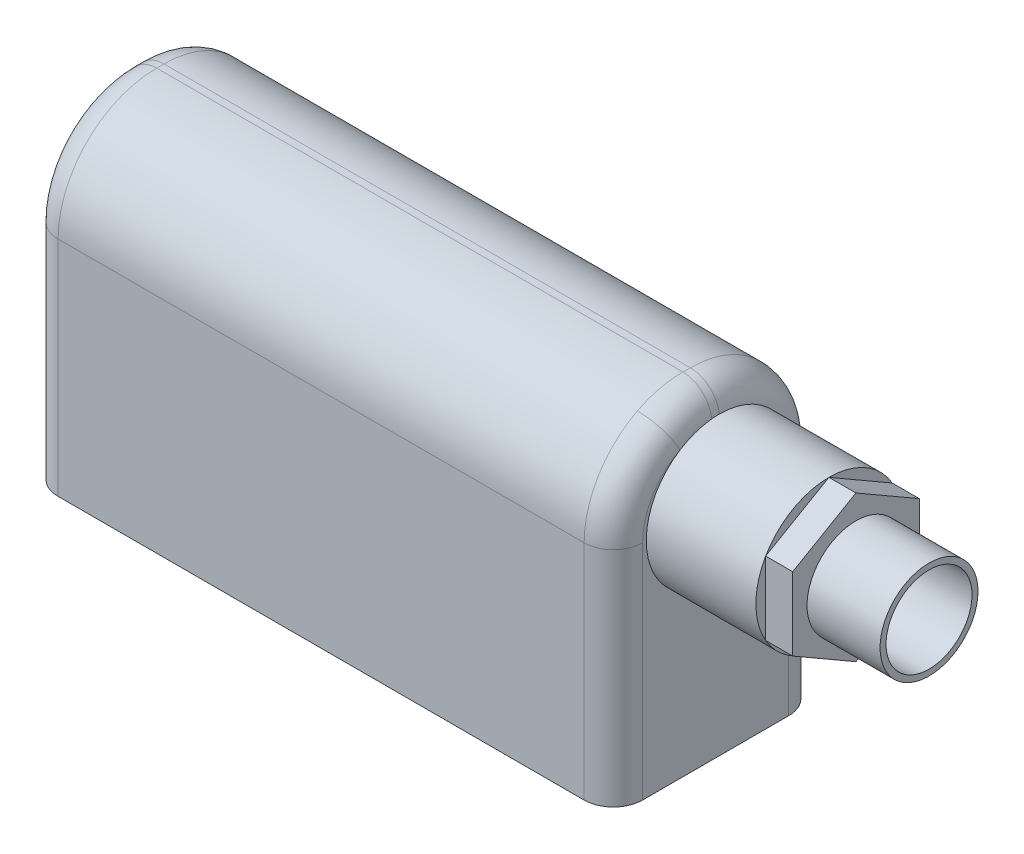
SolidWorks part; units mm, degrees
ref_plane "前视基准面" through (0, 0, 0) normal (0, 0, 1) x (1, 0, 0)
ref_plane "上视基准面" through (0, 0, 0) normal (0, 1, 0) x (1, 0, 0)
ref_plane "右视基准面" through (0, 0, 0) normal (1, 0, 0) x (0, 0, -1)
sketch "草图1" plane through (0, 0, 0) normal (0, 0, 1) x (1, 0, 0)
  line L1 (-40, -22) -> (40, -22)
  line L2 (-40, -22) -> (-40, 22)
  line L3 (-40, 22) -> (40, 22)
  line L4 (40, -22) -> (40, 22)
  line L5 (-40, -22) -> (40, 22) construction
  line L6 (-40, 22) -> (40, -22) construction
  point P0 (0, 0)
  dimension "D1" = 80
  dimension "D2" = 44
extrude "凸台-拉伸1" add sketch "草图1" along normal blind 28 contours L3 L4 L1 L2
fillet "圆角1" radius 13.5 1 edges at (0, 22, 28)
fillet "圆角2" radius 13.5 1 edges at (0, 22, 0)
sketch "草图2" plane through (40, 0, 0) normal (1, 0, 0) x (0, 0, -1)
  circle A0 centre (-13.5, 8.5) radius 10
extrude "凸台-拉伸2" add sketch "草图2" along normal blind 15
sketch "草图3" plane through (55, 0, 0) normal (1, 0, 0) x (0, 0, -1)
  line L1 (-13.5, 18.5) -> (-22.1603, 13.5)
  line L2 (-22.1603, 13.5) -> (-22.1603, 3.5)
  line L3 (-22.1603, 3.5) -> (-13.5, -1.5)
  line L4 (-13.5, -1.5) -> (-4.8397, 3.5)
  line L5 (-4.8397, 3.5) -> (-4.8397, 13.5)
  line L6 (-4.8397, 13.5) -> (-13.5, 18.5)
  circle A0 centre (-13.5, 8.5) radius 8.6603 construction
extrude "凸台-拉伸3" add sketch "草图3" along normal blind 3.7
sketch "草图4" plane through (58.7, 0, 0) normal (1, 0, 0) x (0, 0, -1)
  circle A0 centre (-13.5, 8.5) radius 6.7
extrude "凸台-拉伸4" add sketch "草图4" along normal blind 10
sketch "草图5" plane through (68.7, 0, 0) normal (1, 0, 0) x (0, 0, -1)
  circle A0 centre (-13.5, 8.5) radius 5.8831
extrude "切除-拉伸1" cut sketch "草图5" against normal blind 20
fillet "圆角3" radius 4 8 edges at (40, -6.75, 0) (40, 18.0459, 24.0459) (-40, -6.75, 0) (-40, 18.0459, 3.9541) (-40, 22, 14) (-40, 18.0459, 24.0459) (40, -6.75, 28) (-40, -6.75, 28)
sketch "草图7" plane through (0, -22, 0) normal (0, -1, 0) x (1, 0, 0)
  line L8 (-36, 2) -> (36, 2)
  line L9 (38, 4) -> (38, 24)
  line L10 (36, 26) -> (-36, 26)
  line L11 (-38, 24) -> (-38, 4)
  line L12 (-36, 2) -> (36, 2)
  line L13 (38, 4) -> (38, 24)
  line L14 (36, 26) -> (-36, 26)
  line L15 (-38, 24) -> (-38, 4)
  arc A8 (36, 2) -> (38, 4) centre (36, 4) ccw
  arc A9 (38, 24) -> (36, 26) centre (36, 24) ccw
  arc A10 (-36, 26) -> (-38, 24) centre (-36, 24) ccw
  arc A11 (-38, 4) -> (-36, 2) centre (-36, 4) ccw
  arc A12 (36, 2) -> (38, 4) centre (36, 4) ccw
  arc A13 (38, 24) -> (36, 26) centre (36, 24) ccw
  arc A14 (-36, 26) -> (-38, 24) centre (-36, 24) ccw
  arc A15 (-38, 4) -> (-36, 2) centre (-36, 4) ccw
  dimension "D1" = 2
extrude "切除-拉伸2" cut sketch "草图7" against normal blind 8.5
sketch "草图8" plane through (0, -13.5, 0) normal (0, -1, 0) x (1, 0, 0)
  line L0 (-38, 14) -> (38, 14) construction
  line L1 (-38, 24) -> (-38, 4) construction
  line L2 (38, 4) -> (38, 24) construction
  line L3 (0, 26) -> (0, 2) construction
  line L4 (36, 26) -> (-36, 26) construction
  line L5 (-36, 2) -> (36, 2) construction
  line L6 (-18, 16) -> (-18, 20)
  line L7 (-18, 8) -> (18, 8)
  line L8 (-18, 8) -> (-18, 12)
  line L9 (-18, 20) -> (18, 20)
  line L10 (18, 8) -> (18, 12)
  line L11 (-18, 8) -> (18, 20) construction
  line L12 (-18, 20) -> (18, 8) construction
  line L13 (18, 16) -> (22.5, 16)
  line L14 (-18, 16) -> (-22.5, 16)
  line L15 (18, 16) -> (18, 20)
  line L16 (-18, 12) -> (-22.5, 12)
  line L17 (-22.5, 16) -> (-22.5, 12)
  line L19 (18, 12) -> (22.5, 12)
  line L20 (22.5, 16) -> (22.5, 12)
  point P12 (0, 14)
  dimension "D1" = 36
  dimension "D2" = 12
  dimension "D3" = 4.5
  dimension "D4" = 4.5
  dimension "D5" = 2
  dimension "D6" = 4
  dimension "D7" = 2
  dimension "D8" = 4
extrude "凸台-拉伸5" add sketch "草图8" along normal blind 14
fillet "圆角4" radius 3 1 edges at (0, -27.5, 20)
fillet "圆角5" radius 3 1 edges at (0, -27.5, 8)
sketch "草图9" plane through (0, -13.5, 0) normal (0, -1, 0) x (1, 0, 0)
  line L0 (-38, 14) -> (38, 14) construction
  line L1 (-38, 24) -> (-38, 4) construction
  line L2 (38, 4) -> (38, 24) construction
  line L3 (0, 26) -> (0, 0.7936) construction
  line L4 (36, 26) -> (-36, 26) construction
  circle A0 centre (-24.3, 20) radius 1.5
  circle A1 centre (-18.9, 20) radius 1.5
  circle A2 centre (-13.5, 20) radius 1.5
  circle A3 centre (-8.1, 20) radius 1.5
  circle A4 centre (-2.7, 20) radius 1.5
  circle A5 centre (2.7, 20) radius 1.5
  circle A6 centre (8.1, 20) radius 1.5
  circle A7 centre (13.5, 20) radius 1.5
  circle A8 centre (18.9, 20) radius 1.5
  circle A9 centre (24.3, 20) radius 1.5
  circle A10 centre (-24.3, 8) radius 1.5
  circle A11 centre (-18.9, 8) radius 1.5
  circle A12 centre (-13.5, 8) radius 1.5
  circle A13 centre (-8.1, 8) radius 1.5
  circle A14 centre (-2.7, 8) radius 1.5
  circle A15 centre (2.7, 8) radius 1.5
  circle A16 centre (8.1, 8) radius 1.5
  circle A17 centre (13.5, 8) radius 1.5
  circle A18 centre (18.9, 8) radius 1.5
  circle A19 centre (24.3, 8) radius 1.5
  dimension "D1" = 24.3
  dimension "D2" = 6
  dimension "D3" = 10
  dimension "D4" = 2
extrude "切除-拉伸3" cut sketch "草图9" against normal blind 4
ref_axis "基准轴1" through (48.7, 8.5, 13.5) along (1, 0, 0)
sketch "0_0_Point" plane through (0, -9.5, 0) normal (0, -1, 0) x (1, 0, 0)
  point P0 (24.2869, 8.1168)
sketch "1_0_Point" plane through (0, -9.5, 0) normal (0, -1, 0) x (1, 0, 0)
  point P0 (19.0783, 7.9371)
sketch "2_0_Point" plane through (0, -9.5, 0) normal (0, -1, 0) x (1, 0, 0)
  point P0 (13.2411, 7.6677)
sketch "3_0_Point" plane through (0, -9.5, 0) normal (0, -1, 0) x (1, 0, 0)
  point P0 (7.9427, 7.4881)
sketch "4_0_Point" plane through (0, -9.5, 0) normal (0, -1, 0) x (1, 0, 0)
  point P0 (2.5545, 7.4881)
sketch "5_0_Point" plane through (0, -9.5, 0) normal (0, -1, 0) x (1, 0, 0)
  point P0 (-2.9236, 7.6677)
sketch "6_0_Point" plane through (0, -9.5, 0) normal (0, -1, 0) x (1, 0, 0)
  point P0 (-8.3118, 7.5779)
sketch "7_0_Point" plane through (0, -9.5, 0) normal (0, -1, 0) x (1, 0, 0)
  point P0 (-13.6102, 7.4881)
sketch "8_0_Point" plane through (0, -9.5, 0) normal (0, -1, 0) x (1, 0, 0)
  point P0 (-18.8188, 8.1168)
sketch "9_0_Point" plane through (0, -9.5, 0) normal (0, -1, 0) x (1, 0, 0)
  point P0 (-24.2968, 8.2066)
sketch "10_0_Point" plane through (0, -9.5, 0) normal (0, -1, 0) x (1, 0, 0)
  point P0 (24.1073, 20.0606)
sketch "11_0_Point" plane through (0, -9.5, 0) normal (0, -1, 0) x (1, 0, 0)
  point P0 (18.8987, 20.0606)
sketch "12_0_Point" plane through (0, -9.5, 0) normal (0, -1, 0) x (1, 0, 0)
  point P0 (13.4207, 20.5096)
sketch "13_0_Point" plane through (0, -9.5, 0) normal (0, -1, 0) x (1, 0, 0)
  point P0 (7.9427, 20.5096)
sketch "14_0_Point" plane through (0, -9.5, 0) normal (0, -1, 0) x (1, 0, 0)
  point P0 (2.5545, 20.7791)
sketch "15_0_Point" plane through (0, -9.5, 0) normal (0, -1, 0) x (1, 0, 0)
  point P0 (-2.744, 20.7791)
sketch "16_0_Point" plane through (0, -9.5, 0) normal (0, -1, 0) x (1, 0, 0)
  point P0 (-8.4016, 20.7791)
sketch "17_0_Point" plane through (0, -9.5, 0) normal (0, -1, 0) x (1, 0, 0)
  point P0 (-13.6102, 20.5994)
sketch "18_0_Point" plane through (0, -9.5, 0) normal (0, -1, 0) x (1, 0, 0)
  point P0 (-19.0882, 19.9708)
sketch "19_0_Point" plane through (0, -9.5, 0) normal (0, -1, 0) x (1, 0, 0)
  point P0 (-24.3866, 20.1504)
other "0_0"
ref_axis "基准轴2" through (24.2869, 0.5, 8.1168) along (0, -1, 0)
other "1_0"
ref_axis "基准轴3" through (19.0783, 0.5, 7.9371) along (0, -1, 0)
other "2_0"
ref_axis "基准轴4" through (13.2411, 0.5, 7.6677) along (0, -1, 0)
other "3_0"
ref_axis "基准轴5" through (7.9427, 0.5, 7.4881) along (0, -1, 0)
other "4_0"
ref_axis "基准轴6" through (2.5545, 0.5, 7.4881) along (0, -1, 0)
other "5_0"
ref_axis "基准轴7" through (-2.9236, 0.5, 7.6677) along (0, -1, 0)
other "6_0"
ref_axis "基准轴8" through (-8.3118, 0.5, 7.5779) along (0, -1, 0)
other "7_0"
ref_axis "基准轴9" through (-13.6102, 0.5, 7.4881) along (0, -1, 0)
other "8_0"
ref_axis "基准轴10" through (-18.8188, 0.5, 8.1168) along (0, -1, 0)
other "9_0"
ref_axis "基准轴11" through (-24.2968, 0.5, 8.2066) along (0, -1, 0)
other "10_0"
ref_axis "基准轴12" through (24.1073, 0.5, 20.0606) along (0, -1, 0)
other "11_0"
ref_axis "基准轴13" through (18.8987, 0.5, 20.0606) along (0, -1, 0)
other "12_0"
ref_axis "基准轴14" through (13.4207, 0.5, 20.5096) along (0, -1, 0)
other "13_0"
ref_axis "基准轴15" through (7.9427, 0.5, 20.5096) along (0, -1, 0)
other "14_0"
ref_axis "基准轴16" through (2.5545, 0.5, 20.7791) along (0, -1, 0)
other "15_0"
ref_axis "基准轴17" through (-2.744, 0.5, 20.7791) along (0, -1, 0)
other "16_0"
ref_axis "基准轴18" through (-8.4016, 0.5, 20.7791) along (0, -1, 0)
other "17_0"
ref_axis "基准轴19" through (-13.6102, 0.5, 20.5994) along (0, -1, 0)
other "18_0"
ref_axis "基准轴20" through (-19.0882, 0.5, 19.9708) along (0, -1, 0)
other "19_0"
ref_axis "基准轴21" through (-24.3866, 0.5, 20.1504) along (0, -1, 0)
